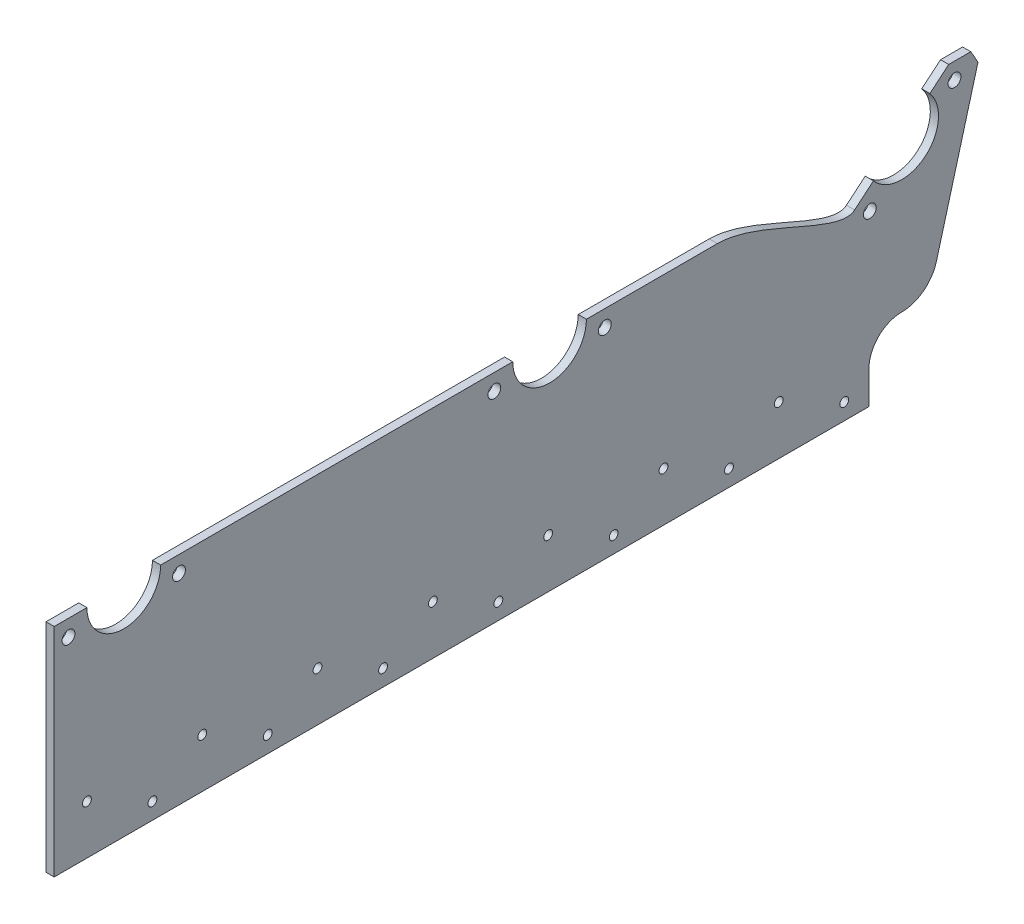
SolidWorks part; units mm, degrees
material "6061 Alloy"
ref_plane "Front Plane" through (0, 0, 0) normal (0, 0, 1) x (1, 0, 0)
ref_plane "Top Plane" through (0, 0, 0) normal (0, 1, 0) x (1, 0, 0)
ref_plane "Right Plane" through (0, 0, 0) normal (1, 0, 0) x (0, 0, -1)
sketch "Sketch1" plane through (0, 0, 0) normal (1, 0, 0) x (0, 0, -1)
  line L0 (-12.7, -12.7) -> (-328.6125, -12.7)
  line L1 (-328.6125, -12.7) -> (-328.6125, 71.4375)
  line L2 (-328.6125, 71.4375) -> (-315.9125, 71.4375)
  line L3 (-287.3375, 71.4375) -> (-150.8125, 71.4375)
  line L5 (10.9449, 80.6213) -> (18.2432, 86.7453)
  line L7 (-328.6125, 12.7) -> (13.4735, 12.7) construction
  line L8 (-12.7, -12.7) -> (-12.7, 0)
  line L9 (0, 12.4079) -> (0, 12.7) construction
  line L10 (13.4735, 22.9788) -> (30.9432, 86.7453)
  line L12 (-10.9449, 62.2537) -> (10.9449, 80.6213) construction
  line L13 (18.2432, 86.7453) -> (30.9432, 86.7453)
  line L14 (-122.2375, 71.4375) -> (-71.4375, 71.4375)
  line L15 (-10.9449, 62.2537) -> (-18.2432, 56.1297)
  line L16 (-328.6125, 15.875) -> (13.4735, 15.875) construction
  line L18 (0, 71.4375) -> (-136.525, 71.4375) construction
  arc A3 (0, 12.7) -> (13.4735, 22.9788) centre (0, 26.67) ccw
  arc A4 (0, 12.7) -> (-12.7, 0) centre (0, 0) ccw
  circle A5 centre (0, 0) radius 12.4079 construction
  arc A6 (-315.9125, 71.4375) -> (-287.3375, 71.4375) centre (-301.625, 71.4375) ccw
  arc A7 (-150.8125, 71.4375) -> (-122.2375, 71.4375) centre (-136.525, 71.4375) ccw
  arc A8 (-10.9449, 62.2537) -> (10.9449, 80.6213) centre (0, 71.4375) ccw
  spline S0 degree 3 poles (-18.2432, 56.1297) (-24.729, 50.6874) (-54.5042, 71.4375) (-71.4375, 71.4375) knots 0 0 0 0 1 1 1 1
  point P4 (-170.6562, -12.7)
  dimension "D1" = 25.4
  dimension "D3" = 12.7
  dimension "D5" = 28.575
  dimension "D6" = 41.275
  dimension "D7" = 13.97
  dimension "D8" = 12.7
  dimension "D10" = 24.8158
  dimension "D13" = 9.5273
  dimension "D14" = 140
  dimension "D15" = 50.8
  dimension "D16" = 50.8
  dimension "D17" = 25.4
  dimension "D2" = 0
  dimension "D4" = 12.7
  dimension "D9" = 12.7
  dimension "D11" = 301.625
  dimension "D12" = 301.625
  dimension "D18" = 3.175
extrude "Boss-Extrude1" add sketch "Sketch1" along normal blind 3.175
hole_wizard "#10 Clearance Hole1" positions "Sketch2" profile "Sketch3" hole size "#10" standard "ANSI Inch" end condition through all
sketch "Sketch2" plane through (3.175, 0, 0) normal (1, 0, 0) x (0, 0, -1)
  line L0 (-323.0562, 65.0875) -> (-280.1937, 65.0875) construction
  line L2 (-157.9562, 65.0875) -> (-115.0938, 65.0875) construction
  line L4 (-12.3356, 52.7974) -> (20.499, 80.3489) construction
  line L6 (-315.9125, 71.4375) -> (-328.6125, 71.4375) construction
  line L7 (-301.625, 65.0875) -> (-301.625, 71.4375) construction
  line L9 (-136.525, 71.4375) -> (-136.525, 65.0875) construction
  line L11 (0, 71.4375) -> (4.0817, 66.5731) construction
  line L14 (18.2432, 86.7453) -> (10.9449, 80.6213) construction
  line L15 (18.2432, 86.7453) -> (10.9449, 80.6213) construction
  point P0 (-323.0562, 65.0875)
  point P2 (-280.1937, 65.0875)
  point P4 (-157.9562, 65.0875)
  point P6 (-115.0938, 65.0875)
  point P8 (-12.3356, 52.7974)
  point P10 (20.499, 80.3489)
  dimension "D1" = 42.8625
  dimension "D2" = 6.35
  dimension "D3" = 6.35
sketch "Sketch3" plane through (3.175, 65.0875, 323.0562) normal (0, 1, 0) x (0, 0, -1)
  line L0 (0, 0) -> (0, 3.175)
  line L1 (0, 3.175) -> (2.4892, 3.175)
  line L2 (2.4892, 3.175) -> (2.4892, 0)
  line L5 (2.4892, 0) -> (0, 0)
  line L11 (0, -6.35) -> (0, 107.95) construction
  dimension "Thru Hole Dia." = 4.9784
  dimension "Thru Hole Depth" = 3.175
chamfer "Chamfer1" distance 5.08 angle 45 1 edges at (1.5875, 86.7453, -30.9432) first distance on face at (1.5875, 54.862, -22.2083)
hole_wizard "1/8 (0.135) Diameter Hole1" positions "Sketch4" profile "Sketch5" hole size "1/8" standard "ANSI Inch"
sketch "Sketch4" plane through (3.175, 0, 0) normal (1, 0, 0) x (0, 0, -1)
  line L0 (-328.6125, -12.7) -> (-12.7, -12.7) construction
  line L1 (-12.7, -12.7) -> (-12.7, 0) construction
  line L2 (-328.6125, 71.4375) -> (-328.6125, -12.7) construction
  point P0 (-22.2504, -6.35)
  point P2 (-47.6504, 6.35)
  point P14 (-66.9607, -6.35)
  point P15 (-92.3607, 6.35)
  point P16 (-111.6711, -6.35)
  point P17 (-137.0711, 6.35)
  point P18 (-156.3814, -6.35)
  point P19 (-181.7814, 6.35)
  point P20 (-201.0918, -6.35)
  point P21 (-226.4918, 6.35)
  point P22 (-245.8021, -6.35)
  point P23 (-271.2021, 6.35)
  point P24 (-290.5125, -6.35)
  point P25 (-315.9125, 6.35)
  dimension "D1" = 6.35
  dimension "D2" = 9.5504
  dimension "D3" = 12.7
  dimension "D4" = 25.4
  dimension "D6" = 12.7
  dimension "D5" = 7
sketch "Sketch5" plane through (3.175, -6.35, 22.2504) normal (0, 1, 0) x (0, 0, -1)
  line L0 (0, 0) -> (0, 17.5402)
  line L1 (0, 17.5402) -> (1.7145, 16.51)
  line L2 (1.7145, 16.51) -> (1.7145, 0)
  line L5 (1.7145, 0) -> (0, 0)
  line L10 (0, 17.5402) -> (-1.7145, 16.51) construction
  line L11 (0, -6.35) -> (0, 107.95) construction
  dimension "Hole Dia." = 3.429
  dimension "Hole Depth" = 16.51
  dimension "Drill Angle" = 118
